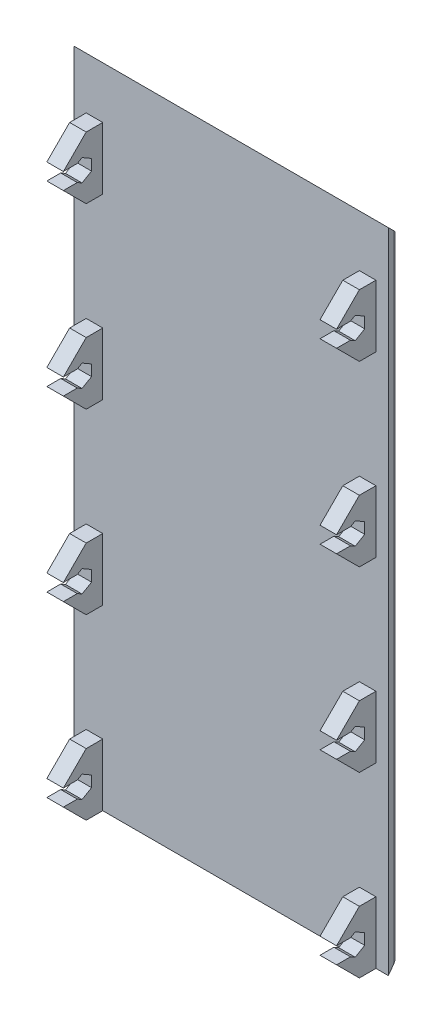
SolidWorks part; units mm, degrees
ref_plane "Front Plane" through (0, 0, 0) normal (0, 0, 1) x (1, 0, 0)
ref_plane "Top Plane" through (0, 0, 0) normal (0, 1, 0) x (1, 0, 0)
ref_plane "Right Plane" through (0, 0, 0) normal (1, 0, 0) x (0, 0, -1)
sketch "Sketch1" plane through (0, 0, 0) normal (0, 1, 0) x (1, 0, 0)
  line L0 (-9.2151, 0) -> (-9.2151, -10)
  line L1 (-9.2151, -10) -> (-5.2151, -10)
  line L2 (-5.2151, -10) -> (-5.2151, 0)
  line L3 (-5.2151, 0) -> (56.7849, 0)
  line L4 (56.7849, 0) -> (56.7849, -10)
  line L5 (56.7849, -10) -> (60.7849, -10)
  line L6 (60.7849, -10) -> (60.7849, 0)
  line L7 (60.7849, 0) -> (63.7849, 0)
  line L8 (-9.2151, 0) -> (-12.2151, 0)
  line L9 (-12.2151, 0) -> (-8.1737, 7)
  line L10 (-8.1737, 7) -> (59.7434, 7)
  line L11 (59.7434, 7) -> (63.7849, 0)
  line L12 (25.7849, 7) -> (25.7849, 0) construction
  dimension "D1" = 3
  dimension "D2" = 10
  dimension "D3" = 70
  dimension "D4" = 7
  dimension "D5" = 4
  dimension "D6" = 60
extrude "Boss-Extrude1" add sketch "Sketch1" along normal blind 156.5
sketch "Sketch4" plane through (60.7849, 0, 0) normal (1, 0, 0) x (0, 0, -1)
  line L0 (0, 156.5) -> (0, 0) construction
  line L1 (-37.5185, 156.5) -> (0, 156.5)
  line L2 (-37.5185, 156.5) -> (-37.5185, 144)
  line L3 (-37.5185, 144) -> (0, 144)
  line L4 (0, 156.5) -> (0, 144)
  line L5 (-37.5185, 156.5) -> (0, 144) construction
  line L6 (-37.5185, 144) -> (0, 156.5) construction
  line L7 (-10, 156.5) -> (0, 156.5) construction
  point P0 (-18.7592, 150.25)
  dimension "D1" = 12.5
extrude "Cut-Extrude1" cut sketch "Sketch4" against normal through all
sketch "Sketch5" plane through (60.7849, 0, 0) normal (1, 0, 0) x (0, 0, -1)
  line L0 (0, 156.5) -> (0, 0) construction
  line L1 (-33.3149, 129) -> (0, 129)
  line L2 (-33.3149, 129) -> (-33.3149, 101)
  line L3 (-33.3149, 101) -> (0, 101)
  line L4 (0, 129) -> (0, 101)
  line L5 (-33.3149, 129) -> (0, 101) construction
  line L6 (-33.3149, 101) -> (0, 129) construction
  line L7 (-10, 144) -> (0, 144) construction
  point P0 (-16.6574, 115)
  dimension "D1" = 28
  dimension "D2" = 15
extrude "Cut-Extrude2" cut sketch "Sketch5" against normal through all
sketch "Sketch6" plane through (0, 0, 0) normal (1, 0, 0) x (0, 0, -1)
  line L0 (-10, 144) -> (-10, 129) construction
  line L1 (-2.7, 137.8279) -> (-5, 139.1558)
  line L2 (-5, 139.1558) -> (-7.3, 137.8279)
  line L3 (-7.3, 137.8279) -> (-7.3, 135.1721)
  line L4 (-7.3, 135.1721) -> (-5, 133.8442)
  line L5 (-5, 133.8442) -> (-2.7, 135.1721)
  line L6 (-2.7, 135.1721) -> (-2.7, 137.8279)
  line L7 (-10, 144) -> (0, 144) construction
  line L8 (-6.15, 138.4919) -> (-10, 138.4919)
  line L9 (-6.15, 134.5081) -> (-10, 134.5081)
  line L10 (-10, 134.5081) -> (-10, 138.4919)
  circle A1 centre (-5, 136.5) radius 2.3 construction
  dimension "D1" = 4.6
  dimension "D2" = 7.5
  dimension "D3" = 5
extrude "Cut-Extrude3" cut sketch "Sketch6" against normal through all and the other way through all contours L10 L9 L4 L3 L2 L8 | L5 L6 L1 L2 L3 L4 region at (0, 136.5, 5) region at (0, 136.5, 8.5351)
pattern_linear "LPattern1" count 4 spacing 43 along (0, -1, 0) of "Cut-Extrude2", "Cut-Extrude3"
chamfer "Chamfer3" distance 7 angle 45 1 edges at (25.7849, 156.5, -7)
fillet "Fillet1" radius 8 2 edges at (-8.1737, 74.75, -7) (59.7434, 74.75, -7)
chamfer "Chamfer5" distance 6 angle 45 16 edges at (58.7849, 43, 10) (58.7849, 144, 10) (58.7849, 129, 10) (-7.2151, 144, 10) (-7.2151, 129, 10) (-7.2151, 101, 10) (-7.2151, 86, 10) (58.7849, 101, 10) (58.7849, 86, 10) (58.7849, 58, 10) (58.7849, 0, 10) (58.7849, 15, 10) (-7.2151, 0, 10) (-7.2151, 15, 10) (-7.2151, 58, 10) (-7.2151, 43, 10)
sketch "Sketch7" plane through (0, 0, -7) normal (0, 0, -1) x (-1, 0, 0)
  line L0 (-4.7849, 98.4573) -> (-46.7849, 98.4573) construction
  line L1 (-4.7849, 98.4573) -> (-4.7849, 51.0427) construction
  line L2 (-46.7849, 98.4573) -> (-46.7849, 51.0427) construction
  line L3 (-4.7849, 51.0427) -> (-46.7849, 51.0427) construction
  line L4 (-4.7849, 98.4573) -> (-4.7849, 91.4573)
  line L5 (-4.7849, 98.4573) -> (-46.7849, 98.4573)
  line L6 (-4.7849, 91.4573) -> (-46.7849, 91.4573)
  line L7 (-46.7849, 98.4573) -> (-46.7849, 91.4573)
  line L8 (3.5549, 51.0427) -> (-4.7849, 51.0427) construction
  line L9 (-4.7849, 83.3744) -> (-46.7849, 59.1256)
  line L10 (-4.7849, 91.4573) -> (-25.7849, 79.3329)
  line L11 (-25.7849, 79.3329) -> (-46.7849, 91.4573)
  line L12 (-18.7849, 91.4573) -> (-25.7849, 87.4158)
  line L13 (-25.7849, 87.4158) -> (-32.7849, 91.4573)
  line L14 (-25.7849, 87.4158) -> (-25.7849, 79.3329) construction
  line L15 (-4.7849, 83.3744) -> (-4.7849, 61.5427)
  line L16 (-46.7849, 59.1256) -> (-46.7849, 51.0427)
  line L17 (-46.7849, 51.0427) -> (-25.7849, 63.1671)
  line L18 (-25.7849, 63.1671) -> (-25.7849, 61.5427)
  line L19 (-11.7849, 79.3329) -> (-11.7849, 61.5427)
  line L20 (-4.7849, 61.5427) -> (-25.7849, 61.5427) construction
  line L21 (-18.7849, 75.2915) -> (-18.7849, 61.5427)
  line L22 (-11.7849, 61.5427) -> (-18.7849, 61.5427) construction
  line L23 (-32.7849, 83.3744) -> (-46.7849, 75.2915)
  line L24 (3.5549, 0) -> (3.5549, 149.5) construction
  line L25 (-46.7849, 75.2915) -> (-32.7849, 67.2085)
  line L26 (-25.7849, 79.3329) -> (-32.7849, 75.2915)
  line L27 (-32.7849, 75.2915) -> (-25.7849, 71.25)
  line L28 (-4.7849, 51.0427) -> (-46.7849, 51.0427) construction
  line L29 (-46.7849, 51.0427) -> (-55.1246, 51.0427) construction
  line L30 (-55.1246, 149.5) -> (-55.1246, 0) construction
  line L31 (-4.7849, 149.5) -> (-4.7849, 98.4573) construction
  line L32 (3.5549, 149.5) -> (-55.1246, 149.5) construction
  line L33 (-4.7849, 51.0427) -> (-4.7849, 0) construction
  line L34 (-55.1246, 0) -> (3.5549, 0) construction
  arc A0 (-4.7849, 61.5427) -> (-25.7849, 61.5427) centre (-15.2849, 61.5427) cw
  arc A1 (-11.7849, 61.5427) -> (-18.7849, 61.5427) centre (-15.2849, 61.5427) cw
  dimension "D11" = 7
  dimension "D12" = 7
  dimension "D2" = 7
  dimension "D3" = 7
  dimension "D4" = 30
  dimension "D5" = 30
  dimension "D6" = 7
  dimension "D7" = 7
  dimension "D8" = 7
  dimension "D9" = 7
  dimension "D13" = 7
  dimension "D15" = 30
extrude "Cut-Extrude4" cut sketch "Sketch7" against normal blind 1 contours L5 L7 L6 L4 | L12 L13 L6 L11 L10 | L27 L26 L11 L23 L25 L9 | L19 A1 L21 L9 L16 L17 L18 A0 L15 region at (25.7849, 94.9573, -7) region at (25.7849, 87.079, -7) region at (35.1182, 75.2915, -7) region at (21.0439, 63.4789, -7)
